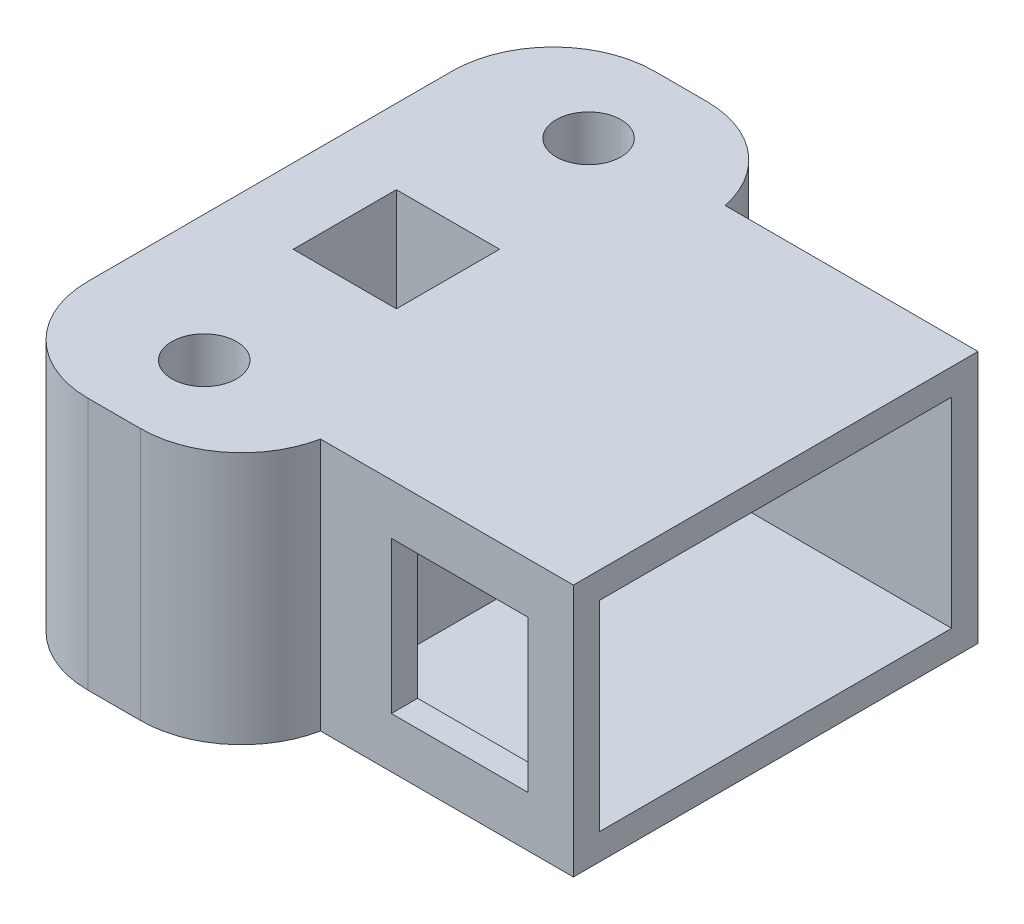
SolidWorks part; units mm, degrees
ref_plane "Front Plane" through (0, 0, 0) normal (0, 0, 1) x (1, 0, 0)
ref_plane "Top Plane" through (0, 0, 0) normal (0, 1, 0) x (1, 0, 0)
ref_plane "Right Plane" through (0, 0, 0) normal (1, 0, 0) x (0, 0, -1)
sketch "Sketch3" plane through (0, 0, 0) normal (0, 1, 0) x (1, 0, 0)
  line L0 (0, -28) -> (0, 28)
  line L1 (0, 28) -> (25, 28)
  line L2 (25, 28) -> (25, 20)
  line L3 (25, 20) -> (50, 20)
  line L4 (50, 20) -> (50, -20)
  line L5 (50, -20) -> (25, -20)
  line L6 (25, -20) -> (25, -28)
  line L7 (25, -28) -> (0, -28)
  point P4 (0, 0)
  dimension "D1" = 25
  dimension "D2" = 56
  dimension "D3" = 40
  dimension "D4" = 25
extrude "Boss-Extrude2" add sketch "Sketch3" along normal blind 25
sketch "Sketch4" plane through (0, 25, 0) normal (0, 1, 0) x (1, 0, 0)
  line L0 (12.5, 28) -> (12.5, -28) construction
  line L1 (25, 28) -> (0, 28) construction
  line L2 (0, -28) -> (25, -28) construction
  line L4 (17.6, -5.1) -> (7.4, -5.1)
  line L5 (17.6, -5.1) -> (17.6, 5.1)
  line L6 (17.6, 5.1) -> (7.4, 5.1)
  line L7 (7.4, -5.1) -> (7.4, 5.1)
  line L8 (17.6, -5.1) -> (7.4, 5.1) construction
  line L9 (17.6, 5.1) -> (7.4, -5.1) construction
  point P6 (12.5, 0)
  dimension "D1" = 10.2
extrude "Cut-Extrude2" cut sketch "Sketch4" against normal offset from surface (22 mm away) 3 up to face at (25, 0, 0)
sketch "Sketch5" plane through (0, 25, 0) normal (0, 1, 0) x (1, 0, 0)
  line L0 (7.4, 0) -> (17.6, 0) construction
  line L3 (7.4, 5.1) -> (7.4, -5.1) construction
  line L4 (17.6, -5.1) -> (17.6, 5.1) construction
  line L5 (12.5, -19) -> (12.5, 19) construction
  circle A0 centre (12.5, 19) radius 3.2
  circle A1 centre (12.5, -19) radius 3.2
  point P9 (12.5, 0)
  point P10 (12.5, 0)
  dimension "D2" = 6.4
  dimension "D1" = 38
extrude "Cut-Extrude3" cut sketch "Sketch5" against normal through all
fillet "Fillet1" radius 10 4 edges at (25, 12.5, 28) (0, 12.5, 28) (25, 12.5, -28) (0, 12.5, -28)
sketch "Sketch8" plane through (50, 0, 0) normal (1, 0, 0) x (0, 0, -1)
  line L0 (20, 12.5) -> (-20, 12.5) construction
  line L1 (20, 25) -> (20, 0) construction
  line L2 (-20, 25) -> (-20, 0) construction
  line L3 (-20, 25) -> (20, 25) construction
  line L4 (-17.4, 2.6) -> (17.4, 2.6)
  line L5 (-17.4, 2.6) -> (-17.4, 22.4)
  line L6 (-17.4, 22.4) -> (17.4, 22.4)
  line L7 (17.4, 2.6) -> (17.4, 22.4)
  line L8 (-17.4, 2.6) -> (17.4, 22.4) construction
  line L9 (-17.4, 22.4) -> (17.4, 2.6) construction
  point P6 (0, 12.5)
  dimension "D1" = 2.6
  dimension "D2" = 2.6
extrude "Cut-Extrude6" cut sketch "Sketch8" against normal blind 25
sketch "Sketch9" plane through (7.4, 0, 0) normal (1, 0, 0) x (0, 0, -1)
  line L0 (-2.6, 3) -> (-2.6, 25) construction
  line L3 (5.1, 25) -> (-5.1, 25) construction
  line L4 (5.1, 3) -> (-5.1, 3) construction
  line L5 (-5.1, 3) -> (-5.1, 25) construction
  circle A0 centre (-2.6, 19) radius 1.6
  circle A1 centre (-2.6, 7) radius 1.6
  dimension "D1" = 3.2
  dimension "D2" = 12
  dimension "D3" = 22
  dimension "D4" = 6
  dimension "D5" = 2.5
extrude "Cut-Extrude7" cut sketch "Sketch9" against normal through all both and the other way through all
sketch "Sketch11" plane through (25, 0, 0) normal (1, 0, 0) x (0, 0, -1)
  line L1 (0.65, 19) -> (-0.975, 21.8146)
  line L2 (-0.975, 21.8146) -> (-4.225, 21.8146)
  line L3 (-4.225, 21.8146) -> (-5.85, 19)
  line L4 (-5.85, 19) -> (-4.225, 16.1854)
  line L5 (-4.225, 16.1854) -> (-0.975, 16.1854)
  line L6 (-0.975, 16.1854) -> (0.65, 19)
  line L7 (0.65, 7) -> (-0.975, 9.8146)
  line L8 (-0.975, 9.8146) -> (-4.225, 9.8146)
  line L9 (-4.225, 9.8146) -> (-5.85, 7)
  line L10 (-5.85, 7) -> (-4.225, 4.1854)
  line L11 (-4.225, 4.1854) -> (-0.975, 4.1854)
  line L12 (-0.975, 4.1854) -> (0.65, 7)
  circle A0 centre (-2.6, 19) radius 3.25 construction
  circle A1 centre (-2.6, 7) radius 3.25 construction
  dimension "D1" = 6.5
extrude "Cut-Extrude9" cut sketch "Sketch11" against normal blind 3.5
sketch "Sketch12" plane through (25, 0, 0) normal (1, 0, 0) x (0, 0, -1)
  line L0 (-2.6, 7) -> (-2.6, 19) construction
  line L1 (-2.6, 13) -> (2.9, 13) construction
  circle A0 centre (2.9, 13) radius 3.5316
  dimension "D1" = 5.5
extrude "Cut-Extrude10" cut sketch "Sketch12" against normal blind 7
sketch "Sketch13" plane through (0, 0, 17.4) normal (0, 0, -1) x (-1, 0, 0)
  line L0 (-50, 12.5) -> (-25, 12.5) construction
  line L1 (-50, 22.4) -> (-50, 2.6) construction
  line L2 (-25, 22.4) -> (-25, 2.6) construction
  line L4 (-45.5, 5) -> (-32, 5)
  line L5 (-45.5, 5) -> (-45.5, 20)
  line L6 (-45.5, 20) -> (-32, 20)
  line L7 (-32, 5) -> (-32, 20)
  line L8 (-45.5, 5) -> (-32, 20) construction
  line L9 (-45.5, 20) -> (-32, 5) construction
  point P6 (-38.75, 12.5)
  dimension "D1" = 15
  dimension "D2" = 13.5
  dimension "D3" = 7
extrude "Cut-Extrude11" cut sketch "Sketch13" against normal through all
sketch "Sketch14" plane through (0, 0, 0) normal (-1, 0, 0) x (0, 0, 1)
  circle A0 centre (2.6, 7) radius 3.5
  circle A1 centre (2.6, 19) radius 3.5
  dimension "D1" = 7
extrude "Cut-Extrude12" cut sketch "Sketch14" against normal blind 3
sketch "Sketch15" plane through (0, 0, 0) normal (0, -1, 0) x (1, 0, 0)
  circle A0 centre (12.5, 19) radius 6.5
  circle A1 centre (12.5, -19) radius 6.5
  dimension "D1" = 13
extrude "Cut-Extrude13" cut sketch "Sketch15" against normal blind 6
sketch "Sketch16" plane through (0, 0, -20) normal (0, 0, -1) x (-1, 0, 0)
  line L0 (-39.3013, 0) -> (-39.3013, 25) construction
  line L1 (-50, 0) -> (-25, 0) construction
  line L2 (-50, 25) -> (-25, 25) construction
  text T0 "<b>PULL</b>\r\n<b>HERE</b>" font "Century Gothic" height 7
extrude "Boss-Extrude3" add sketch "Sketch16" along normal blind 0.5
